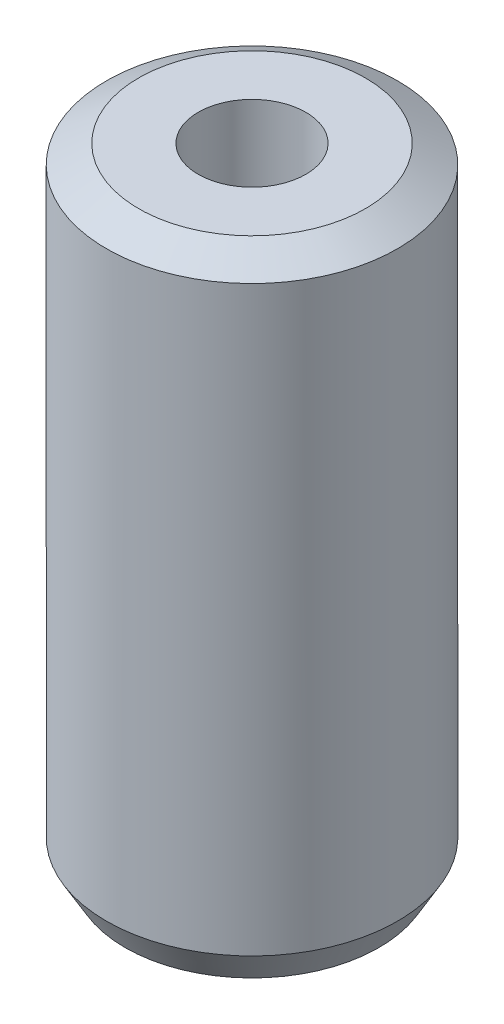
SolidWorks part; units mm, degrees
ref_plane "Front Plane" through (0, 0, 0) normal (0, 0, 1) x (1, 0, 0)
ref_plane "Top Plane" through (0, 0, 0) normal (0, 1, 0) x (1, 0, 0)
ref_plane "Right Plane" through (0, 0, 0) normal (1, 0, 0) x (0, 0, -1)
sketch "Sketch1" plane through (0, 0, 0) normal (0, 1, 0) x (1, 0, 0)
  circle A0 centre (0, 0) radius 15
  dimension "SHAFT_OD" = 30
extrude "Boss-Extrude1" add sketch "Sketch1" along normal blind 65.2592
sketch "Sketch2" plane through (0, 0, 0) normal (0, 1, 0) x (1, 0, 0)
  circle A0 centre (0, 0) radius 5.5473
  dimension "BORE_D" = 11.0946
extrude "Cut-Extrude1" cut sketch "Sketch2" along normal through all
chamfer "Chamfer1" distance 1.9158 angle 60 2 edges at (0, 65.2592, 15) (0, 0, 15) first distance on face at (0, 65.2592, 15) first distance on face at (0, 0, 5.5473)
